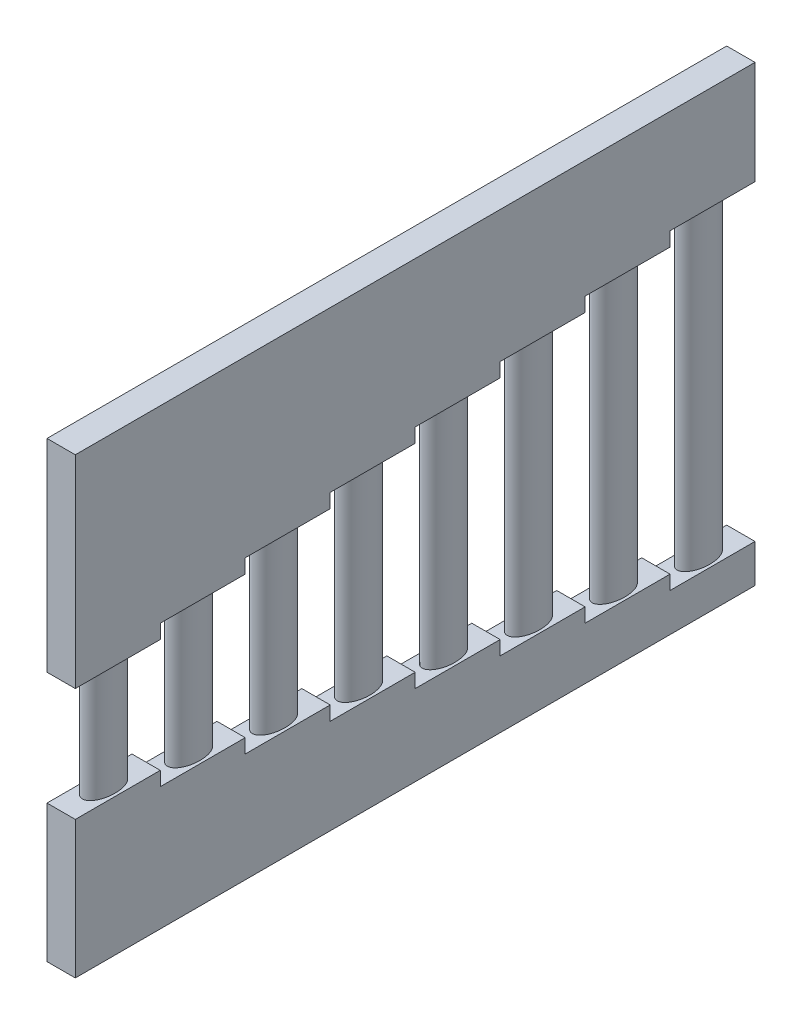
SolidWorks part; units mm, degrees
note: The reader was unsure of these and kept them because the rebuilt part matched: shared geometry of "Sketch8<4>", "Sketch13<3>", "Sketch14<3>", "Sketch15<3>", "Sketch16<3>", "Sketch17<3>", "Sketch18<3>", "Sketch19<3>".
ref_plane "Front Plane" through (0, 0, 0) normal (0, 0, 1) x (1, 0, 0)
ref_plane "Top Plane" through (0, 0, 0) normal (0, 1, 0) x (1, 0, 0)
ref_plane "Right Plane" through (0, 0, 0) normal (1, 0, 0) x (0, 0, -1)
sketch "Sketch2" plane through (0, 0, 0) normal (0, 0, 1) x (1, 0, 0)
  line L0 (0, 0) -> (0, -20.3) construction
  line L1 (0, -20.3) -> (-7.23, -20.3) construction
  line L2 (-7.23, -20.3) -> (-7.23, -34)
  line L3 (-7.23, -34) -> (-9.23, -34)
  line L4 (-9.23, -34) -> (-9.23, -2)
  line L5 (-9.23, -2) -> (-7.23, -2)
  line L6 (-7.23, -2) -> (-7.23, -20.3)
  point P10 (-7.23, -20.3)
  dimension "D1" = 18.3
  dimension "D2" = 13.7
extrude "Boss-Extrude1" add sketch "Sketch2" along normal blind 48
sketch "Sketch7" plane through (-7.23, 0, 0) normal (1, 0, 0) x (0, 0, -1)
  line L0 (0, -20.3) -> (-48, -20.3) construction
  line L1 (-48, -34) -> (-48, -2) construction
  line L2 (-48, -16.3) -> (-48, -24.3)
  line L3 (-48, -24.3) -> (-42, -24.3)
  line L4 (-42, -24.3) -> (-42, -25.3)
  line L5 (-42, -25.3) -> (-36, -25.3)
  line L6 (-36, -25.3) -> (-36, -26.3)
  line L7 (-36, -26.3) -> (-30, -26.3)
  line L8 (-30, -26.3) -> (-30, -27.3)
  line L9 (-30, -27.3) -> (-24, -27.3)
  line L10 (-24, -27.3) -> (-24, -28.3)
  line L11 (-24, -28.3) -> (-18, -28.3)
  line L12 (-18, -28.3) -> (-18, -29.3)
  line L13 (-18, -29.3) -> (-12, -29.3)
  line L14 (-12, -29.3) -> (-12, -30.3)
  line L15 (-12, -30.3) -> (-6, -30.3)
  line L16 (-6, -30.3) -> (-6, -31.3)
  line L17 (-6, -31.3) -> (0, -31.3)
  line L18 (0, -34) -> (0, -2) construction
  line L19 (0, -31.3) -> (0, -9.3)
  line L21 (-48, -16.3) -> (-42, -16.3)
  line L22 (-6, -9.3) -> (0, -9.3)
  line L23 (-6, -10.3) -> (-6, -9.3)
  line L24 (-12, -10.3) -> (-6, -10.3)
  line L25 (-12, -11.3) -> (-12, -10.3)
  line L26 (-18, -11.3) -> (-12, -11.3)
  line L27 (-18, -12.3) -> (-18, -11.3)
  line L28 (-24, -12.3) -> (-18, -12.3)
  line L29 (-24, -13.3) -> (-24, -12.3)
  line L30 (-30, -13.3) -> (-24, -13.3)
  line L31 (-30, -14.3) -> (-30, -13.3)
  line L32 (-36, -14.3) -> (-30, -14.3)
  line L33 (-36, -15.3) -> (-36, -14.3)
  line L34 (-42, -15.3) -> (-36, -15.3)
  line L35 (-42, -16.3) -> (-42, -15.3)
  dimension "D1" = 8
extrude "Cut-Extrude4" cut sketch "Sketch7" against normal blind 2
sketch "Sketch8" plane through (0, -24.3, 0) normal (0, 1, 0) x (1, 0, 0)
  line L0 (-8.23, -48) -> (-8.23, -42) construction
  line L1 (-9.23, -48) -> (-7.23, -48) construction
  line L2 (-9.23, -42) -> (-7.23, -42) construction
  ellipse E0 centre (-8.23, -45) end of major axis (-8.23, -43.5) minor radius 0.8
extrude "Cut-Extrude6" cut sketch "Sketch8" against normal blind 1 and the other way blind 9 contours E0
sketch "Sketch13" plane through (0, -25.3, 0) normal (0, 1, 0) x (1, 0, 0)
  line L0 (-8.23, -42) -> (-8.23, -36)
  line L1 (-9.23, -42) -> (-7.23, -42) construction
  line L2 (-9.23, -36) -> (-7.23, -36) construction
  ellipse E0 centre (-8.23, -39) end of major axis (-8.23, -37.5) minor radius 0.8
sketch "Sketch14" plane through (0, -26.3, 0) normal (0, 1, 0) x (1, 0, 0)
  line L0 (-8.23, -36) -> (-8.23, -30)
  line L1 (-9.23, -36) -> (-7.23, -36) construction
  line L2 (-9.23, -30) -> (-7.23, -30) construction
  ellipse E0 centre (-8.23, -33) end of major axis (-8.23, -31.5) minor radius 0.8
sketch "Sketch15" plane through (0, -27.3, 0) normal (0, 1, 0) x (1, 0, 0)
  line L0 (-8.23, -30) -> (-8.23, -24)
  line L1 (-9.23, -30) -> (-7.23, -30) construction
  line L2 (-9.23, -24) -> (-7.23, -24) construction
  ellipse E0 centre (-8.23, -27) end of major axis (-8.23, -25.5) minor radius 0.8
sketch "Sketch16" plane through (0, -28.3, 0) normal (0, 1, 0) x (1, 0, 0)
  line L0 (-8.23, -24) -> (-8.23, -18)
  line L1 (-9.23, -24) -> (-7.23, -24) construction
  line L2 (-9.23, -18) -> (-7.23, -18) construction
  ellipse E0 centre (-8.23, -21) end of major axis (-8.23, -19.5) minor radius 0.8
sketch "Sketch17" plane through (0, -29.3, 0) normal (0, 1, 0) x (1, 0, 0)
  line L0 (-8.23, -18) -> (-8.23, -12)
  line L1 (-9.23, -18) -> (-7.23, -18) construction
  line L2 (-9.23, -12) -> (-7.23, -12) construction
  ellipse E0 centre (-8.23, -15) end of major axis (-8.23, -13.5) minor radius 0.8
sketch "Sketch18" plane through (0, -30.3, 0) normal (0, 1, 0) x (1, 0, 0)
  line L0 (-8.23, -12) -> (-8.23, -6)
  line L1 (-9.23, -12) -> (-7.23, -12) construction
  line L2 (-9.23, -6) -> (-7.23, -6) construction
  ellipse E0 centre (-8.23, -9) end of major axis (-8.23, -7.5) minor radius 0.8
sketch "Sketch19" plane through (0, -31.3, 0) normal (0, 1, 0) x (1, 0, 0)
  line L0 (-8.23, -6) -> (-8.23, 0)
  line L1 (-9.23, -6) -> (-7.23, -6) construction
  line L2 (-9.23, 0) -> (-7.23, 0) construction
  ellipse E0 centre (-8.23, -3) end of major axis (-8.23, -1.5) minor radius 0.8
extrude "Cut-Extrude7" cut sketch "Sketch13" against normal blind 1 and the other way blind 11 contours E0
extrude "Cut-Extrude8" cut sketch "Sketch14" against normal blind 1 and the other way blind 13 contours E0
extrude "Cut-Extrude9" cut sketch "Sketch15" against normal blind 1 and the other way blind 15 contours E0
extrude "Cut-Extrude10" cut sketch "Sketch16" against normal blind 1 and the other way blind 17 contours E0
extrude "Cut-Extrude11" cut sketch "Sketch17" against normal blind 1 and the other way blind 19 contours E0
extrude "Cut-Extrude12" cut sketch "Sketch18" against normal blind 1 and the other way blind 21 contours E0
extrude "Cut-Extrude13" cut sketch "Sketch19" against normal blind 1 and the other way blind 23 contours E0
extrude "Boss-Extrude2" add sketch "Sketch8<4>" along normal blind 10 contours E0
sketch "Sketch8<4>" plane through (0, -24.3, 0) normal (0, 1, 0) x (1, 0, 0) same geometry as "Sketch8"
extrude "Boss-Extrude3" add sketch "Sketch13<3>" along normal blind 10 separate body contours E0
sketch "Sketch13<3>" plane through (0, -25.3, 0) normal (0, 1, 0) x (1, 0, 0) same geometry as "Sketch13"
extrude "Boss-Extrude4" add sketch "Sketch14<3>" along normal blind 12 separate body contours E0
sketch "Sketch14<3>" plane through (0, -26.3, 0) normal (0, 1, 0) x (1, 0, 0) same geometry as "Sketch14"
extrude "Boss-Extrude5" add sketch "Sketch15<3>" along normal blind 14 separate body contours E0
sketch "Sketch15<3>" plane through (0, -27.3, 0) normal (0, 1, 0) x (1, 0, 0) same geometry as "Sketch15"
extrude "Boss-Extrude6" add sketch "Sketch16<3>" along normal blind 16 separate body contours E0
sketch "Sketch16<3>" plane through (0, -28.3, 0) normal (0, 1, 0) x (1, 0, 0) same geometry as "Sketch16"
extrude "Boss-Extrude7" add sketch "Sketch17<3>" along normal blind 18 separate body contours E0
sketch "Sketch17<3>" plane through (0, -29.3, 0) normal (0, 1, 0) x (1, 0, 0) same geometry as "Sketch17"
extrude "Boss-Extrude8" add sketch "Sketch18<3>" along normal blind 20 separate body contours E0
sketch "Sketch18<3>" plane through (0, -30.3, 0) normal (0, 1, 0) x (1, 0, 0) same geometry as "Sketch18"
extrude "Boss-Extrude9" add sketch "Sketch19<3>" along normal blind 22 separate body contours E0
sketch "Sketch19<3>" plane through (0, -31.3, 0) normal (0, 1, 0) x (1, 0, 0) same geometry as "Sketch19"
